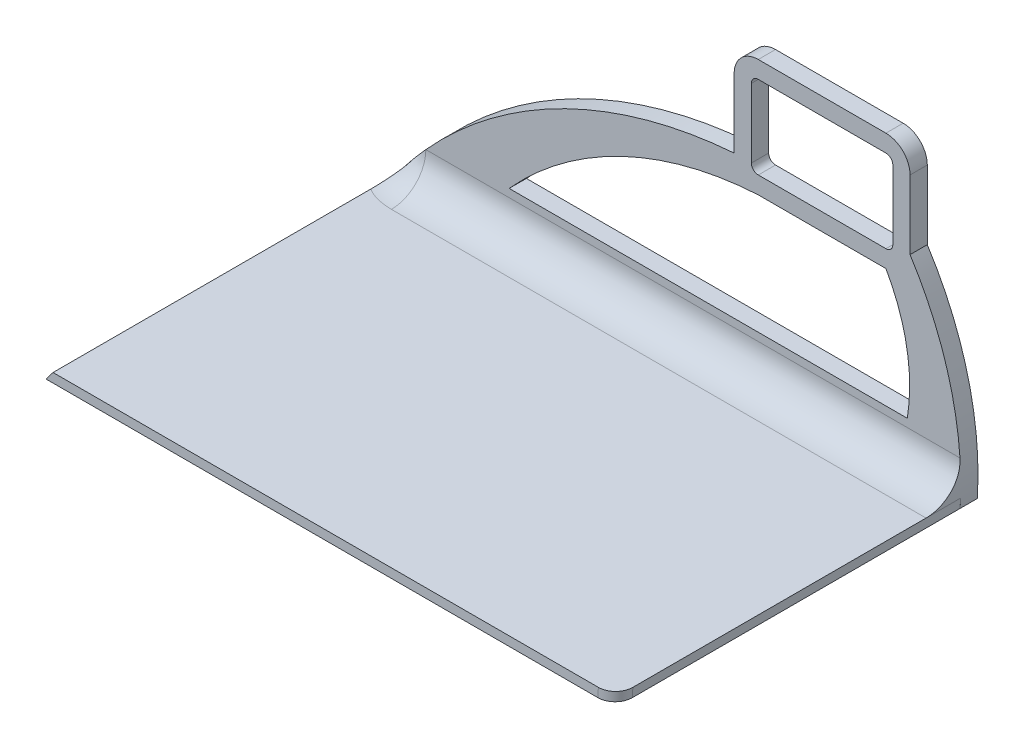
SolidWorks part; units mm, degrees
ref_plane "Alzado" through (0, 0, 0) normal (0, 0, 1) x (1, 0, 0)
ref_plane "Planta" through (0, 0, 0) normal (0, 1, 0) x (1, 0, 0)
ref_plane "Vista lateral" through (0, 0, 0) normal (1, 0, 0) x (0, 0, -1)
sketch "Croquis1" plane through (0, 0, 0) normal (0, 0, 1) x (1, 0, 0)
  line L0 (-18.5, 17) -> (18.5, 17)
  line L1 (-18.5, -12) -> (18.5, -12)
  line L2 (-20.5, -10) -> (-20.5, 10)
  line L3 (-18.5, 12) -> (18.5, 12)
  line L4 (20.5, -10) -> (20.5, 10)
  line L5 (-20.5, -12) -> (20.5, 12) construction
  line L6 (-20.5, 12) -> (20.5, -12) construction
  line L7 (25.5, -10) -> (25.5, 10)
  line L8 (-18.5, -17) -> (18.5, -17)
  line L9 (-25.5, -10) -> (-25.5, 10)
  line L10 (0, 33.6157) -> (0, -86.667) construction
  line L11 (-125, -66.4853) -> (40, -66.4853)
  line L12 (-90.7272, -51.4853) -> (24.7018, -51.4853)
  arc A0 (-18.5, -12) -> (-20.5, -10) centre (-18.5, -10) cw
  arc A1 (18.5, -12) -> (20.5, -10) centre (18.5, -10) ccw
  arc A2 (18.5, 12) -> (20.5, 10) centre (18.5, 10) cw
  arc A3 (-20.5, 10) -> (-18.5, 12) centre (-18.5, 10) cw
  arc A4 (18.5, 17) -> (25.5, 10) centre (18.5, 10) cw
  arc A7 (-25.5, 10) -> (-18.5, 17) centre (-18.5, 10) cw
  arc A8 (25.5, -10) -> (40, -66.4853) centre (-53.3194, -60.337) cw
  arc A9 (-25.5, -10) -> (-125, -66.4853) centre (-15.3765, -143.711) ccw
  arc A10 (-90.7272, -51.4853) -> (-18.5, -17) centre (-12.7785, -121.8635) cw
  arc A11 (18.5, -17) -> (24.7018, -51.4853) centre (-27.3114, -43.039) cw
  arc A12 (-24.3676, -24.9572) -> (-90.7272, -51.4853) centre (-15.3765, -143.711) ccw construction
  arc A13 (12.8581, -18.0736) -> (24.7018, -51.4853) centre (-53.3194, -60.337) cw construction
  arc A14 (-18.5, -17) -> (-25.5, -10) centre (-18.5, -10) cw construction
  arc A15 (18.5, -17) -> (25.5, -10) centre (18.5, -10) ccw construction
  point P0 (0, 0)
  dimension "D3" = 2
  dimension "D1" = 41
  dimension "D2" = 24
  dimension "D5" = 165
  dimension "D6" = 40
  dimension "D4" = 5
  dimension "D7" = 15
extrude "Saliente-Extruir2" add sketch "Croquis1" along normal blind 5
sketch "Croquis2" plane through (0, 0, 5) normal (0, 0, 1) x (1, 0, 0)
  line L0 (-125, -66.4853) -> (40, -66.4853)
  line L1 (-125, -66.4853) -> (40, -66.4853) construction
  line L2 (-125, -66.4853) -> (40, -66.4853)
  line L3 (40, -66.4853) -> (40.1375, -63.818)
  line L4 (40.1375, -63.818) -> (-122.9566, -63.818)
  line L5 (-125, -66.4853) -> (-122.9566, -63.818)
  arc A0 (40, -66.4853) -> (25.5, -10) centre (-53.3194, -60.337) ccw construction
  line M12 (-125, -66.4853) -> (40, -66.4853)
extrude "Saliente-Extruir3" add sketch "Croquis2" along normal blind 100 contours L5 L3 L4 M12 region at (-41.9558, -65.1543, 5)
fillet "Redondeo1" radius 10 1 edges at (-41.4095, -63.818, 5)
fillet "Redondeo2" radius 5 1 edges at (40.0688, -65.1517, 105)
